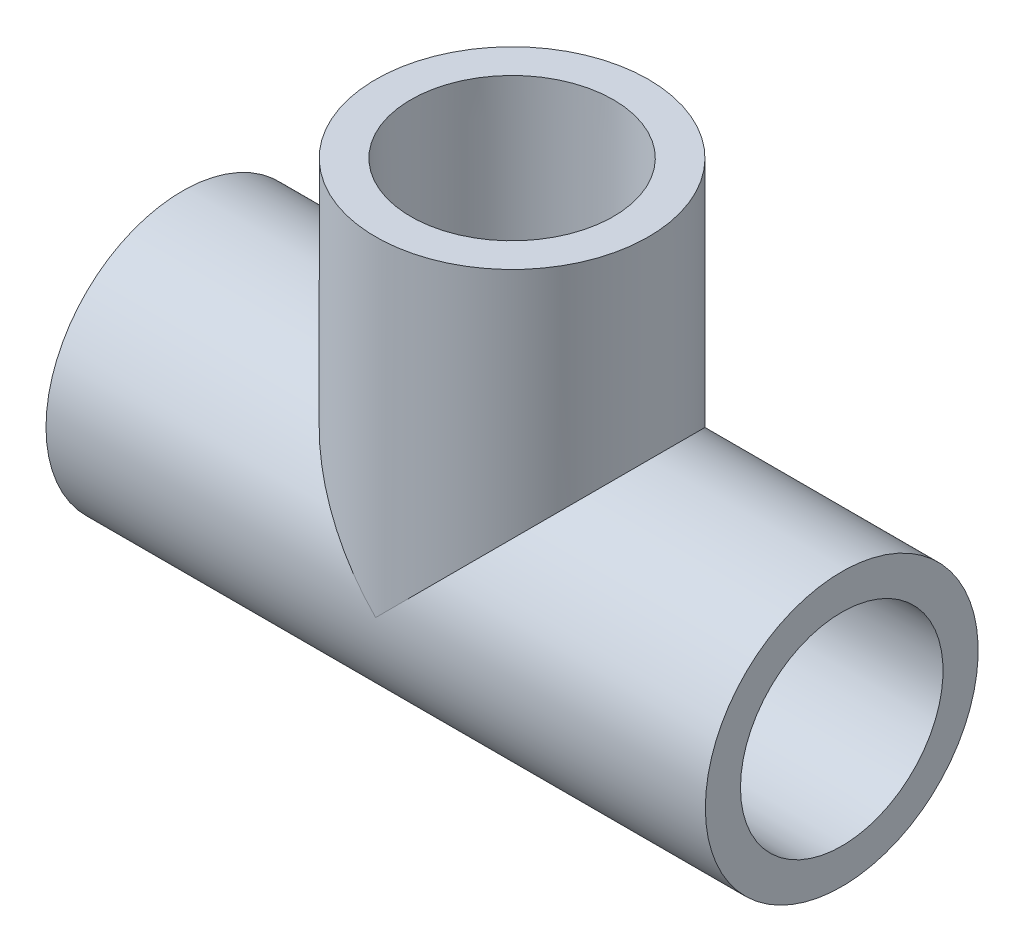
SolidWorks part; units mm, degrees
ref_plane "Front Plane" through (0, 0, 0) normal (0, 0, 1) x (1, 0, 0)
ref_plane "Top Plane" through (0, 0, 0) normal (0, 1, 0) x (1, 0, 0)
ref_plane "Right Plane" through (0, 0, 0) normal (1, 0, 0) x (0, 0, -1)
sketch "Sketch0" plane through (0, 0, 0) normal (0, 0, 1) x (1, 0, 0)
  line L0 (-35.052, 0) -> (0, 0) construction
  line L1 (0, 0) -> (0, 35.052) construction
  line L2 (-12.7, 0) -> (0, 0) construction
  line L3 (0, 0) -> (0, 12.7) construction
  line L4 (-35.052, 14.5034) -> (-35.052, -14.5034) construction
  line L5 (-12.7, 10.6172) -> (-35.052, 10.7696) construction
  line L6 (-12.7, 10.6172) -> (-12.7, -10.6172) construction
  line L7 (-12.7, -10.6172) -> (-35.052, -10.7696) construction
  line L8 (-35.052, 10.7696) -> (-35.052, -10.7696) construction
  line L9 (-14.5034, 35.052) -> (14.5034, 35.052) construction
  line L10 (-10.7696, 35.052) -> (10.7696, 35.052) construction
  line L11 (10.7696, 35.052) -> (10.6172, 12.7) construction
  line L12 (10.6172, 12.7) -> (-10.6172, 12.7) construction
  line L13 (-10.6172, 12.7) -> (-10.7696, 35.052) construction
  line L14 (-12.7, 6.9342) -> (-12.7, -6.9342) construction
  line L18 (-6.9342, 12.7) -> (6.9342, 12.7) construction
  dimension "H" = 35.052
  dimension "G" = 12.7
  dimension "M" = 29.0068
  dimension "OD A" = 21.5392
  dimension "OD B" = 21.2344
  dimension "ID" = 13.8684
sketch "Sketch1" plane through (0, 0, 0) normal (0, 0, 1) x (1, 0, 0)
  line L0 (-35.052, 0) -> (0, 0) construction
  line L1 (-35.052, 0) -> (0, 0) construction
  line L3 (-35.052, -14.5034) -> (-12.7, -14.5034)
  line L4 (-35.052, -14.5034) -> (-35.052, -10.7696)
  line L5 (-35.052, -10.7696) -> (-12.7, -10.6172)
  line L6 (-12.7, -14.5034) -> (-12.7, -10.6172)
revolve "Revolve1" add sketch "Sketch1" angle 360 about L1
mirror "Mirror1" about plane through (0, 0, 0) normal (1, 0, 0) of bodies 102
sketch "Sketch2" plane through (0, 0, 0) normal (0, 0, 1) x (1, 0, 0)
  line L0 (10.7696, 35.052) -> (10.6172, 12.7)
  line L1 (10.6172, 12.7) -> (14.5034, 12.7)
  line L2 (14.5034, 12.7) -> (14.5034, 35.052)
  line L3 (14.5034, 35.052) -> (10.7696, 35.052)
  line L4 (0, 0) -> (0, 35.052) construction
  line L5 (0, 0) -> (0, 35.052) construction
revolve "Revolve2" add sketch "Sketch2" angle 360 about L5
sketch "Sketch3" plane through (-12.7, 0, 0) normal (1, 0, 0) x (0, 0, -1)
  line L0 (-14.5034, 12.7) -> (14.5034, 12.7) construction
  line L2 (7.0042, 12.7) -> (-7.0042, 12.7)
  circle A1 centre (0, 0) radius 14.5034 construction
  arc A3 (-7.0042, 12.7) -> (7.0042, 12.7) centre (0, 0) ccw
extrude "Boss-Extrude1" add sketch "Sketch3" along normal up to surface (25.4 mm away) up to face at (12.7, 0, 10.6172)
sketch "Sketch4" plane through (0, 12.7, 0) normal (0, -1, 0) x (1, 0, 0)
  line L0 (12.7, -7.0042) -> (12.7, 7.0042)
  line L1 (-12.7, -7.0042) -> (-12.7, 7.0042)
  circle A0 centre (0, 0) radius 14.5034 construction
  arc A1 (12.7, 7.0042) -> (-12.7, 7.0042) centre (0, 0) ccw
  arc A2 (-12.7, -7.0042) -> (12.7, -7.0042) centre (0, 0) ccw
  circle A3 centre (0, 0) radius 14.5034 construction
  circle A4 centre (0, 0) radius 14.5034 construction
extrude "Boss-Extrude2" add sketch "Sketch4" along normal up to surface (12.7 mm away) up to plane "Top Plane"
sketch "Sketch5" plane through (-12.7, 0, 0) normal (-1, 0, 0) x (0, 0, 1)
  line L0 (0, 10.6172) -> (0, -10.6172) construction
  circle A0 centre (0, 0) radius 6.9342
extrude "Cut-Extrude1" cut sketch "Sketch5" against normal up to surface (25.4 mm away) up to face at (12.7, 0, 10.6172)
sketch "Sketch6" plane through (0, 12.7, 0) normal (0, 1, 0) x (1, 0, 0)
  circle A0 centre (0, 0) radius 6.9342
extrude "Cut-Extrude2" cut sketch "Sketch6" against normal up to vertex (12.7 mm away) up to point (0, 0, 0)
other "CPoint1" parameters "Diameter"=12.7, "StubLength"=152.4
ref_axis "Axis1" through (22.7, 0, 0) along (-1, 0, 0)
other "CPoint2" parameters "Diameter"=12.7, "StubLength"=152.4
ref_axis "Axis2" through (0, 22.7, 0) along (0, -1, 0)
other "CPoint3" parameters "Diameter"=12.7, "StubLength"=19.05
ref_axis "Axis3" through (-22.7, 0, 0) along (1, 0, 0)
other "RPoint1"
